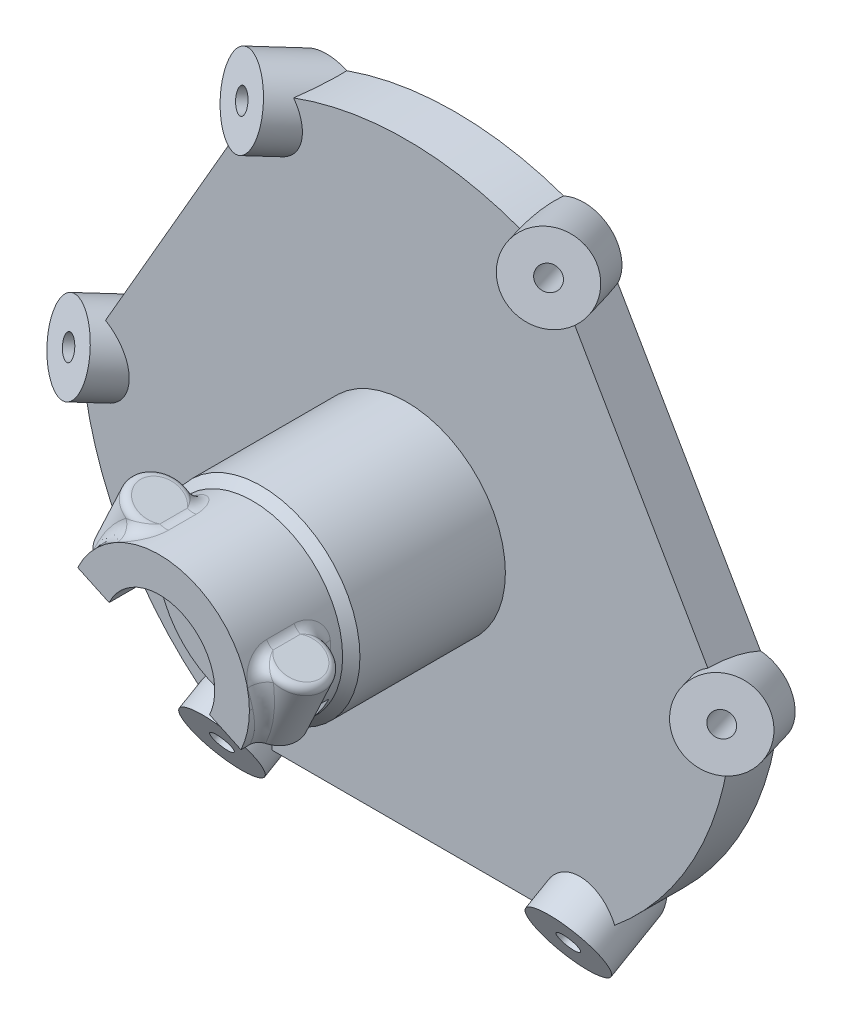
SolidWorks part; units mm, degrees
ref_plane "Front Plane" through (0, 0, 0) normal (0, 0, 1) x (1, 0, 0)
ref_plane "Top Plane" through (0, 0, 0) normal (0, 1, 0) x (1, 0, 0)
ref_plane "Right Plane" through (0, 0, 0) normal (1, 0, 0) x (0, 0, -1)
sketch "Sketch1" plane through (0, 0, 0) normal (0, 0, 1) x (1, 0, 0)
  line L0 (-17.8109, 39.1506) -> (-42.8109, -4.1506) construction
  line L1 (0, 0) -> (-30.3109, 17.5) construction
  line L2 (0, 43.0116) -> (0, -35) construction
  line L3 (42.8109, -4.1506) -> (17.8109, 39.1506) construction
  line L4 (-25, -35) -> (25, -35) construction
  circle A0 centre (0, 0) radius 11.25 construction
  circle A1 centre (0, 0) radius 43.0116 construction
  point P5 (-30.3109, 17.5)
  point P15 (0, 0)
  dimension "D1" = 22.5
  dimension "D2" = 60
  dimension "D3" = 50
  dimension "D4" = 35
  dimension "D5" = 3
ref_axis "Axis1" through (0, 0, 0) along (0, 0, 1)
ref_plane "Plane1" through (-7.5777, 4.375, 15.1554) normal (-0.433, 0.25, 0.866) x (-0.5, -0.866, 0)
ref_plane "Plane2" through (7.5777, 4.375, 15.1554) normal (0.433, 0.25, 0.866) x (-0.5, 0.866, 0)
ref_plane "Plane3" through (0, -8.75, 15.1554) normal (0, -0.5, 0.866) x (1, 0, 0)
sketch "Sketch2" plane through (0, 0, 0) normal (0, 0, 1) x (1, 0, 0)
  line L9 (-21.275, 41.1506) -> (-46.275, -2.1506)
  line L10 (-20.6497, 42.2337) -> (-46.9003, -3.2337)
  line L12 (46.275, -2.1506) -> (21.275, 41.1506)
  line L13 (46.9003, -3.2337) -> (20.6497, 42.2337)
  line L15 (-25, -39) -> (25, -39)
  line L16 (-26.2506, -39) -> (26.2506, -39)
  circle A0 centre (0, 0) radius 11.25
  arc A4 (20.6497, 42.2337) -> (-20.6497, 42.2337) centre (0, 0) ccw
  circle A5 centre (0, 0) radius 47.0116
  arc A6 (-46.9003, -3.2337) -> (-26.2506, -39) centre (0, 0) ccw
  arc A7 (26.2506, -39) -> (46.9003, -3.2337) centre (0, 0) ccw
  dimension "D5" = 22.5
  dimension "D1" = 4
  dimension "D2" = 4
  dimension "D3" = 4
  dimension "D4" = 4
extrude "Boss-Extrude1" add sketch "Sketch2" along normal blind 7
sketch "Sketch3" plane through (-7.5777, 4.375, 15.1554) normal (-0.433, 0.25, 0.866) x (-0.5, -0.866, 0)
  circle A0 centre (-25, -30.3109) radius 1.6
  circle A1 centre (-25, -30.3109) radius 5.6
  circle A2 centre (25, -30.3109) radius 1.6
  circle A3 centre (25, -30.3109) radius 5.6
  dimension "D1" = 3.2
  dimension "D2" = 11.2
extrude "Boss-Extrude2" add sketch "Sketch3" along normal blind 10
extrude "Cut-Extrude1" cut sketch "Sketch3<2>" along normal through all and the other way through all contours A0 | A2
sketch "Sketch3<2>" plane through (-7.5777, 4.375, 15.1554) normal (-0.433, 0.25, 0.866) x (-0.5, -0.866, 0) same geometry as "Sketch3"
pattern_circular "CirPattern1" count 3 over 360 about axis through (0, 0, 0) along (0, 0, 1) of "Boss-Extrude2", "Cut-Extrude1"
sketch "Sketch5" plane through (0, 0, 0) normal (0, 0, -1) x (-1, 0, 0)
  circle A0 centre (0, 0) radius 78.1561
extrude "Cut-Extrude3" cut sketch "Sketch5" along normal through all
sketch "Sketch6" plane through (0, 0, 0) normal (0, 1, 0) x (1, 0, 0)
  line L0 (11.15, 0) -> (11.15, -26) construction
  line L1 (-43.0116, 0) -> (43.0116, 0) construction
  line L2 (11.15, -26) -> (5, -26) construction
  line L3 (5, -26) -> (5, -30) construction
  line L4 (5, -30) -> (8, -30) construction
  line L5 (8, -30) -> (8, -33)
  line L6 (8, -33) -> (6, -33) construction
  line L7 (6, -33) -> (6, -39) construction
  line L8 (6, -39) -> (8, -39) construction
  line L9 (8, -39) -> (8, -42.7)
  line L10 (8, -42.7) -> (0, -42.7) construction
  line L11 (0, 0) -> (0, -44.1609) construction
  line L12 (0, -42.7) -> (0, 0) construction
  line L13 (0, 0) -> (11.15, 0) construction
  line L14 (8, -42.7) -> (13, -42.7)
  line L15 (13, -42.7) -> (13, -29.2426)
  line L16 (13, -29.2426) -> (14.25, -27.9926)
  line L17 (14.25, -27.9926) -> (14.25, -7)
  line L18 (-19.4001, -7) -> (19.4001, -7) construction
  line L19 (14.25, -7) -> (11.25, -7)
  line L20 (8, -30) -> (11.25, -26.75)
  line L21 (11.25, -26.75) -> (11.25, -7)
  line L22 (8, -39) -> (8, -33)
  dimension "D1" = 26
  dimension "D2" = 3.7
  dimension "D3" = 6
  dimension "D4" = 3
  dimension "D5" = 42.7
  dimension "D6" = 8
  dimension "D7" = 6
  dimension "D8" = 11.15
  dimension "D9" = 5
  dimension "D10" = 5
  dimension "D11" = 3
  dimension "D13" = 45
  dimension "D14" = 3
revolve "Revolve1" add sketch "Sketch6" angle 360 about L12
sketch "Sketch7" plane through (0, 0, 42.7) normal (0, 0, 1) x (1, 0, 0)
  line L0 (-12.9149, 6.0223) -> (12.9149, -6.0223)
  line L1 (0, 43.0116) -> (0, -35) construction
  circle A0 centre (0, 0) radius 14.25 construction
  arc A1 (-12.9149, 6.0223) -> (12.9149, -6.0223) centre (0, 0) ccw
  dimension "D1" = 65
extrude "Cut-Extrude5" cut sketch "Sketch7" against normal blind 12.7
sketch "Sketch8" plane through (0, 0, 0) normal (-0.4226, -0.9063, 0) x (-0.9063, 0.4226, 0)
  line L0 (8, -39.0318) -> (8, -34.3682)
  line L1 (-8, -39.0318) -> (-8, -34.3682)
  line L2 (-8, -42.7) -> (-8, -30) construction
  line L3 (-13, -42.7) -> (-8, -42.7) construction
  line L4 (0, -42.7) -> (0, -30) construction
  line L5 (-8, -42.7) -> (8, -42.7) construction
  line L6 (-13, -30) -> (13, -30) construction
  circle A0 centre (-11.25, -36.7) radius 2
  circle A1 centre (-11.25, -36.7) radius 4
  circle A2 centre (11.25, -36.7) radius 4
  circle A3 centre (11.25, -36.7) radius 2
  line M1 (-8, -42.7) -> (-8, -30)
  line M3 (-13, -30) -> (-13, -42.7)
  dimension "D1" = 11.25
  dimension "D2" = 4
  dimension "D3" = 8
  dimension "D4" = 6
extrude "Boss-Extrude3" add sketch "Sketch8<4>" against normal blind 10 contours A1 A0 M3 | A1 A0 M3 M1 | A2 L0 A3 | A0 M3 | A3 | A0 M3 region at (-7.3483, 3.4266, 36.7) region at (9.3277, -4.3496, 40.4864) region at (12.6429, -5.8955, 36.7) region at (10.1512, -4.7336, 36.7) region at (11.8731, -5.5365, 36.7) region at (-10.196, 4.7545, 36.7)
sketch "Sketch8<4>" plane through (0, 0, 0) normal (-0.4226, -0.9063, 0) x (-0.9063, 0.4226, 0) same geometry as "Sketch8"
extrude "Cut-Extrude7" cut sketch "Sketch8" against normal blind 8 contours A0 | A3
fillet "Fillet2" radius 1 2 edges at (-9.595, 15.508, 36.7) (18.0474, 2.6181, 36.7)
fillet "Fillet1" radius 2 10 edges at (12.8948, -1.6502, 32.8641) (12.9447, -1.1979, 40.576) (11.7545, 5.5525, 36.7) (-9.5528, 8.8173, 32.8641) (-3.3022, 12.5736, 36.7) (-9.2383, 9.1462, 40.576) (11.9665, 5.0798, 33.9514) (11.971, 5.0691, 39.4657) (-3.8116, 12.4287, 33.9343) (-3.8006, 12.432, 39.4486)
